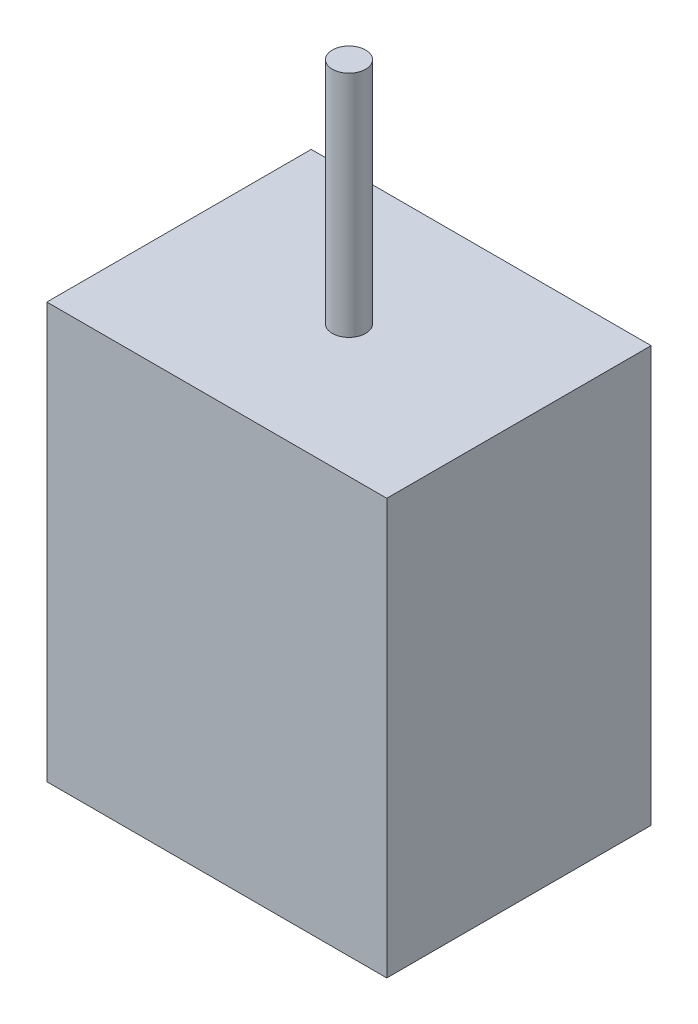
SolidWorks part; units mm, degrees
ref_plane "Front Plane" through (0, 0, 0) normal (0, 0, 1) x (1, 0, 0)
ref_plane "Top Plane" through (0, 0, 0) normal (0, 1, 0) x (1, 0, 0)
ref_plane "Right Plane" through (0, 0, 0) normal (1, 0, 0) x (0, 0, -1)
sketch "Sketch1" plane through (0, 0, 0) normal (0, 1, 0) x (1, 0, 0)
  line L1 (-7.65, 5.95) -> (7.65, 5.95)
  line L2 (-7.65, 5.95) -> (-7.65, -5.95)
  line L3 (-7.65, -5.95) -> (7.65, -5.95)
  line L4 (7.65, 5.95) -> (7.65, -5.95)
  line L5 (-7.65, 5.95) -> (7.65, -5.95) construction
  line L6 (-7.65, -5.95) -> (7.65, 5.95) construction
  circle A0 centre (0, 0) radius 0.75
  point P0 (0, 0)
  dimension "D3" = 1.5
  dimension "D1" = 15.3
  dimension "D2" = 11.9
extrude "Boss-Extrude1" add sketch "Sketch1" along normal blind 18.7 contours L4 L1 L2 L3 A0 region at (0, 0, -5.7562)
extrude "Boss-Extrude2" add sketch "Sketch1<4>" along normal blind 29 contours A0 region at (0, 0, 0)
sketch "Sketch1<4>" plane through (0, 0, 0) normal (0, 1, 0) x (1, 0, 0) same geometry as "Sketch1"
